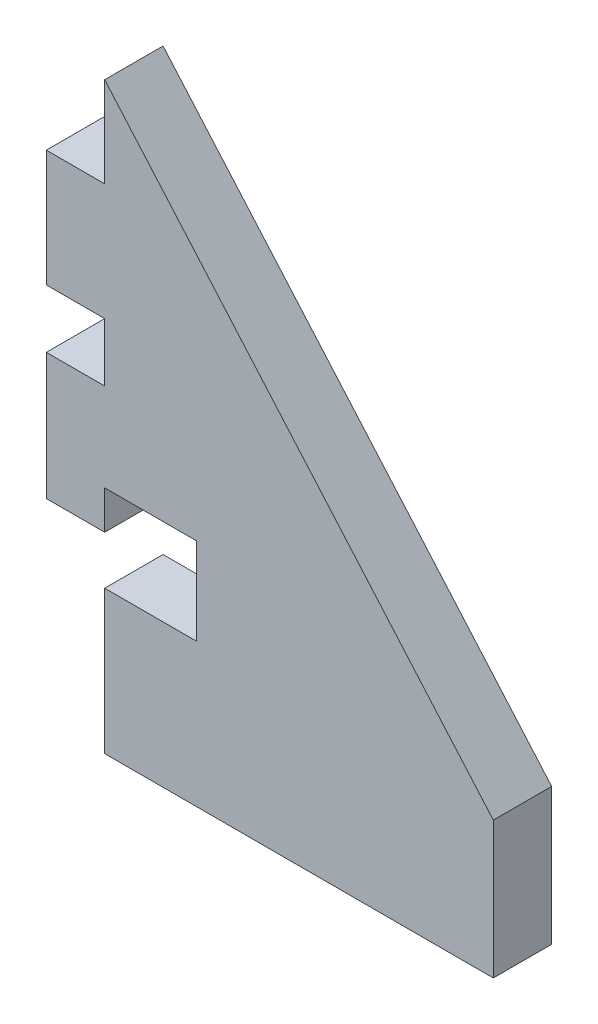
SolidWorks part; units mm, degrees
ref_plane "Front Plane" through (0, 0, 0) normal (0, 0, 1) x (1, 0, 0)
ref_plane "Top Plane" through (0, 0, 0) normal (0, 1, 0) x (1, 0, 0)
ref_plane "Right Plane" through (0, 0, 0) normal (1, 0, 0) x (0, 0, -1)
sketch "Sketch1" plane through (0, 0, 0) normal (0, 0, 1) x (1, 0, 0)
  line L0 (-12.3467, 38.1) -> (-18.6967, 38.1)
  line L1 (-18.6967, 38.1) -> (-18.6967, 25.4)
  line L2 (-18.6967, 25.4) -> (-12.3467, 25.4)
  line L3 (-12.3467, 25.4) -> (-12.3467, 19.05)
  line L4 (-12.3467, 19.05) -> (-18.6967, 19.05)
  line L5 (-18.6967, 19.05) -> (-18.6967, 5.2705)
  line L6 (-18.6967, 5.2705) -> (-12.3467, 5.2705)
  line L7 (-12.3467, 5.2705) -> (-12.3467, 9.4558)
  line L8 (-2.3467, 5.2705) -> (-2.3467, 0)
  line L9 (-5.7109, 0) -> (-12.3467, 0) construction
  line L10 (-2.3467, 0) -> (-12.3467, 0)
  line L11 (-12.3467, 0) -> (-12.3467, -15.5875)
  line L12 (-12.3467, -15.5875) -> (29.9353, -15.5875)
  line L13 (177.2366, -15.5875) -> (-12.3467, -15.5875) construction
  line L14 (29.9353, -15.5875) -> (29.9353, -0.7105)
  line L15 (29.9353, -0.7105) -> (-12.3467, 47.9125)
  line L16 (-12.3467, 47.9125) -> (-12.3467, 38.1)
  line L17 (-2.3467, 5.2705) -> (-2.3467, 9.4558)
  line L18 (-2.3467, 9.4558) -> (-12.3467, 9.4558)
  dimension "D1" = 10
extrude "Boss-Extrude1" add sketch "Sketch1" along normal blind 6.35
